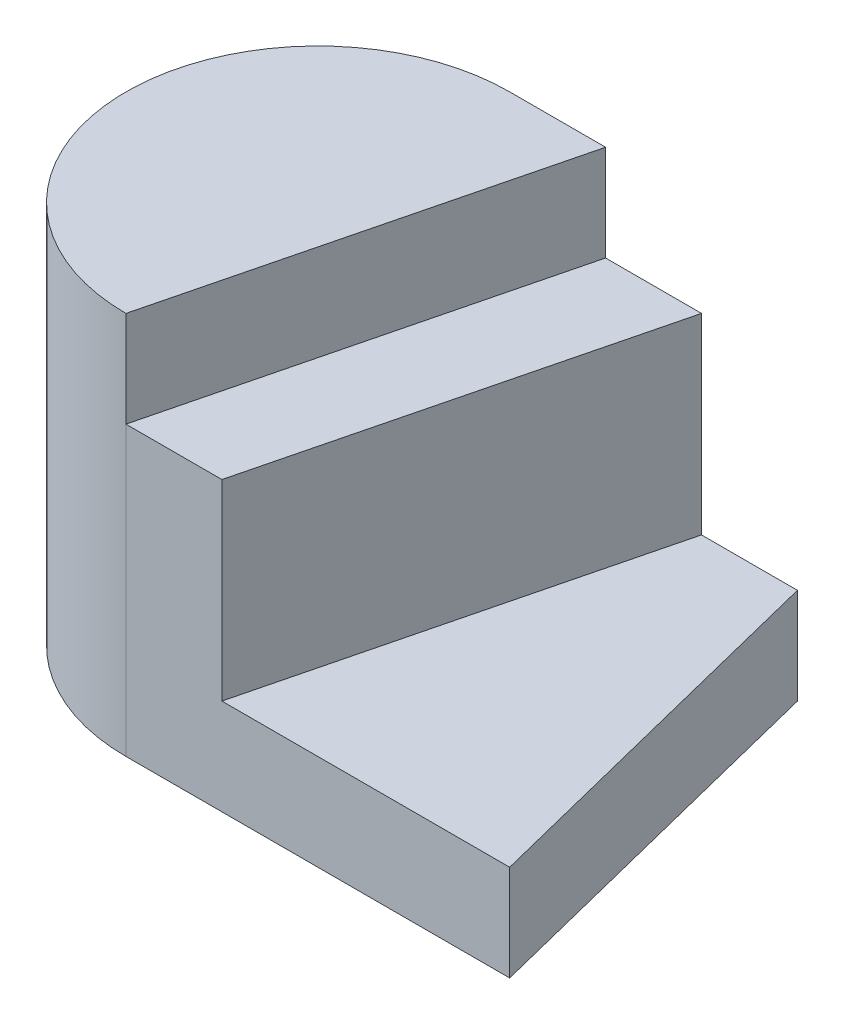
SolidWorks part; units mm, degrees
ref_plane "前基準面" through (0, 0, 0) normal (0, 0, 1) x (1, 0, 0)
ref_plane "上基準面" through (0, 0, 0) normal (0, 1, 0) x (1, 0, 0)
ref_plane "右基準面" through (0, 0, 0) normal (1, 0, 0) x (0, 0, -1)
sketch "草圖1" plane through (0, 0, 0) normal (0, 1, 0) x (1, 0, 0)
  line L0 (0, 0) -> (27.1901, 0) construction
  line L1 (0, 10) -> (15, 10)
  line L2 (15, 10) -> (20, -10)
  line L3 (20, -10) -> (0, -10)
  line L4 (0, -10) -> (5, 10)
  line L5 (5, 10) -> (10, 10)
  line L6 (10, 10) -> (5, -10)
  arc A0 (0, 10) -> (0, -10) centre (0, 0) ccw
  dimension "D1" = 20
  dimension "D2" = 15
  dimension "D3" = 20
  dimension "D4" = 5
  dimension "D5" = 5
extrude "填料-伸長2" add sketch "草圖1" along normal blind 20 contours L1 A0 L4 region at (-2.817, 0, -0.8048)
extrude "填料-伸長3" add sketch "草圖1<4>" along normal blind 15 contours L0 L4 L3 L6 | L4 L0 L6 L1 region at (6.25, 0, -5) region at (3.75, 0, 5)
sketch "草圖1<4>" plane through (0, 0, 0) normal (0, 1, 0) x (1, 0, 0) same geometry as "草圖1"
extrude "填料-伸長4" add sketch "草圖1<5>" along normal blind 5 contours L0 L6 L3 L2 | L6 L0 L2 L1 region at (12.5, 0, -4.4444) region at (12.5, 0, 5.3333)
sketch "草圖1<5>" plane through (0, 0, 0) normal (0, 1, 0) x (1, 0, 0) same geometry as "草圖1"
